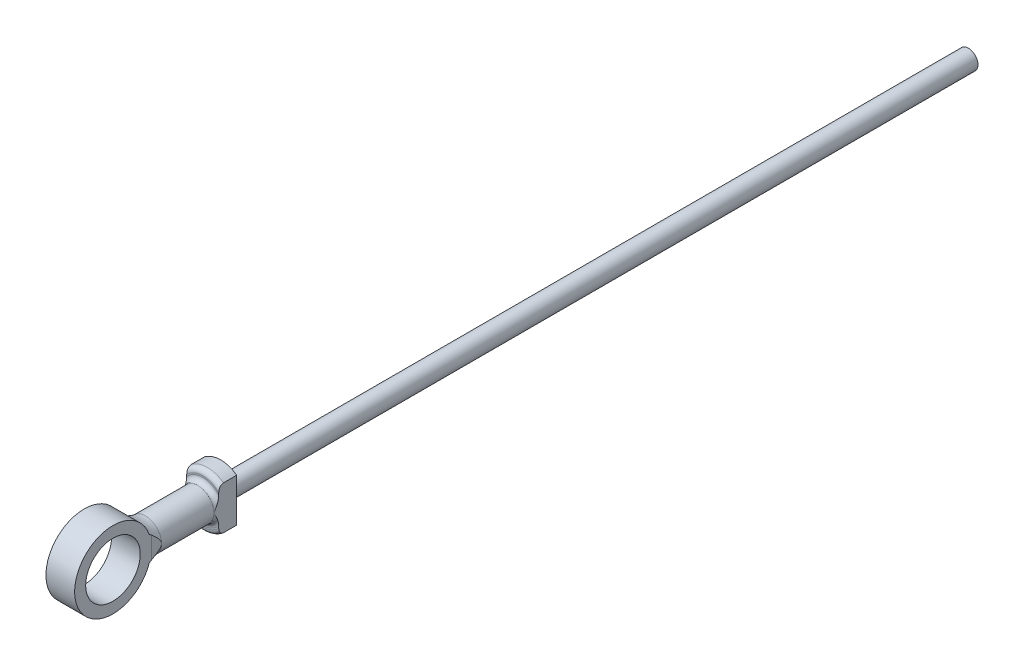
SolidWorks part; units mm, degrees
ref_plane "Front" through (0, 0, 0) normal (0, 0, 1) x (1, 0, 0)
ref_plane "Top" through (0, 0, 0) normal (0, 1, 0) x (1, 0, 0)
ref_plane "Right" through (0, 0, 0) normal (1, 0, 0) x (0, 0, -1)
sketch "Sketch1" plane through (0, 0, 0) normal (0, 0, 1) x (1, 0, 0)
  circle A0 centre (0, 0) radius 2
extrude "Boss-Extrude1" add sketch "Sketch1" along normal blind 156.17
sketch "Sketch2" plane through (0, 0, 156.17) normal (0, 0, 1) x (1, 0, 0)
  circle A0 centre (0, 0) radius 5.62
extrude "Boss-Extrude2" add sketch "Sketch2" along normal blind 3.75 separate body
sketch "Sketch3" plane through (0, 0, 159.92) normal (0, 0, 1) x (1, 0, 0)
  circle A0 centre (0, 0) radius 3.3428
extrude "Boss-Extrude3" add sketch "Sketch3" along normal blind 14.75
fillet "Fillet4" radius 1 1 edges at (3.3428, 0, 159.92)
fillet "Fillet5" radius 1 1 edges at (5.62, 0, 159.92)
sketch "Sketch4" plane through (0, 0, 0) normal (1, 0, 0) x (0, 0, -1)
  line L0 (-156.17, 0) -> (-181.67, 0) construction
  line L1 (-156.17, 2) -> (-156.17, -2) construction
  line L2 (-160.92, 3.3428) -> (-174.67, 3.3428) construction
  line L3 (-171.8667, 3.3428) -> (-171.8667, -3.3428)
  circle A0 centre (-181.67, 0) radius 8
  circle A1 centre (-181.67, 0) radius 5.7
  spline S0 degree 2 poles (-175.0692, 4.5199) (-173.6297, 3.5351) (-171.8667, 3.3428) knots 0 0 0 1 1 1
  spline S1 degree 2 poles (-175.0692, -4.5199) (-173.6297, -3.5351) (-171.8667, -3.3428) knots 0 0 0 1 1 1
  point P15 (-173.67, 0)
  dimension "D1" = 2.3
extrude "Boss-Extrude4" add sketch "Sketch4" along normal blind 5 and the other way blind 5 contours A0 region at (0, 2.2988, 174.2439)
sketch "Sketch7" plane through (0, 0, 0) normal (0, 1, 0) x (1, 0, 0)
  line L0 (0, -189.67) -> (0, -171.8667) construction
  line L1 (-5, -189.67) -> (5, -189.67) construction
  line L2 (3.3428, -173.67) -> (0, -173.67) construction
  line L3 (3, -173.67) -> (3.3428, -171.8667)
  line L4 (3, -173.67) -> (3, -190.9165)
  line L5 (3, -190.9165) -> (8.6584, -190.9165)
  line L6 (8.6584, -190.9165) -> (8.6584, -171.8667)
  line L7 (3.3428, -171.8667) -> (8.6584, -171.8667)
  line L8 (-3, -190.9165) -> (-8.6584, -190.9165)
  line L9 (-3, -173.67) -> (-3, -190.9165)
  line L10 (-3, -173.67) -> (-3.3428, -171.8667)
  line L11 (-3.3428, -171.8667) -> (-8.6584, -171.8667)
  line L12 (-8.6584, -190.9165) -> (-8.6584, -171.8667)
  line L13 (-8.6584, -160.92) -> (-8.6584, -154.6842)
  line L14 (3.3428, -160.92) -> (8.6584, -160.92)
  line L15 (3.3428, -160.92) -> (3.3428, -154.6842)
  line L16 (3.3428, -154.6842) -> (8.6584, -154.6842)
  line L17 (8.6584, -160.92) -> (8.6584, -154.6842)
  line L18 (-3.3428, -154.6842) -> (-8.6584, -154.6842)
  line L19 (-3.3428, -160.92) -> (-3.3428, -154.6842)
  line L20 (-3.3428, -160.92) -> (-8.6584, -160.92)
  point P3 (3, -173.67)
  dimension "D1" = 3
revolve "Revolve2" add sketch "Sketch4<4>" angle 360 about L0 region at (0, -2.0088, 173.0241)
sketch "Sketch4<4>" plane through (0, 0, 0) normal (1, 0, 0) x (0, 0, -1) same geometry as "Sketch4"
extrude "Cut-Extrude2" cut sketch "Sketch7" against normal through all both and the other way through all
combine bodies "Combine1" operation type add bodies to combine 109 110
ref_axis "Axis1" through (0, 0, -80.9) along (0, 0, 1)
